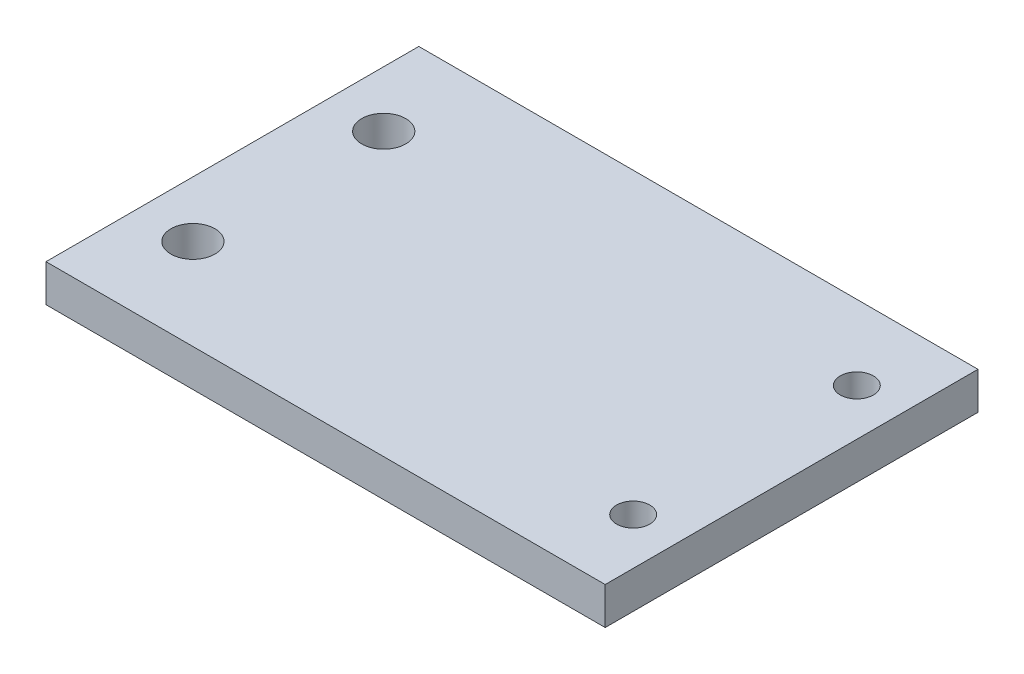
SolidWorks part; units mm, degrees
ref_plane "Front" through (0, 0, 0) normal (0, 0, 1) x (1, 0, 0)
ref_plane "Top" through (0, 0, 0) normal (0, 1, 0) x (1, 0, 0)
ref_plane "Right" through (0, 0, 0) normal (1, 0, 0) x (0, 0, -1)
sketch "Sketch1" plane through (0, 0, 0) normal (0, 1, 0) x (1, 0, 0)
  line L1 (0, 0) -> (38.1, 0)
  line L2 (0, 0) -> (0, 25.4)
  line L3 (0, 25.4) -> (38.1, 25.4)
  line L4 (38.1, 0) -> (38.1, 25.4)
  dimension "D1" = 25.4
  dimension "D2" = 38.1
extrude "Boss-Extrude1" add sketch "Sketch1" along normal blind 2.54
sketch "Sketch2" plane through (0, 2.54, 0) normal (0, 1, 0) x (1, 0, 0)
  line L0 (0, 12.7) -> (38.1, 12.7) construction
  line L1 (0, 25.4) -> (0, 0) construction
  line L2 (38.1, 0) -> (38.1, 25.4) construction
  circle A0 centre (3.81, 19.2) radius 1.5
  circle A1 centre (3.81, 6.2) radius 1.5
  dimension "D1" = 3
  dimension "D2" = 6.5
  dimension "D3" = 3.81
extrude "Cut-Extrude3" cut sketch "Sketch2" along normal through all and the other way through all
sketch "Sketch5" plane through (0, 2.54, 0) normal (0, 1, 0) x (1, 0, 0)
  line L0 (0, 12.7) -> (38.1, 12.7) construction
  line L1 (0, 25.4) -> (0, 0) construction
  line L2 (38.1, 0) -> (38.1, 25.4) construction
  line L3 (38.1, 25.4) -> (0, 25.4) construction
  circle A0 centre (34.925, 20.32) radius 1.1303
  circle A1 centre (34.925, 5.08) radius 1.1303
  dimension "D1" = 2.2606
  dimension "D2" = 5.08
  dimension "D3" = 3.175
extrude "Cut-Extrude4" cut sketch "Sketch5" against normal through all
